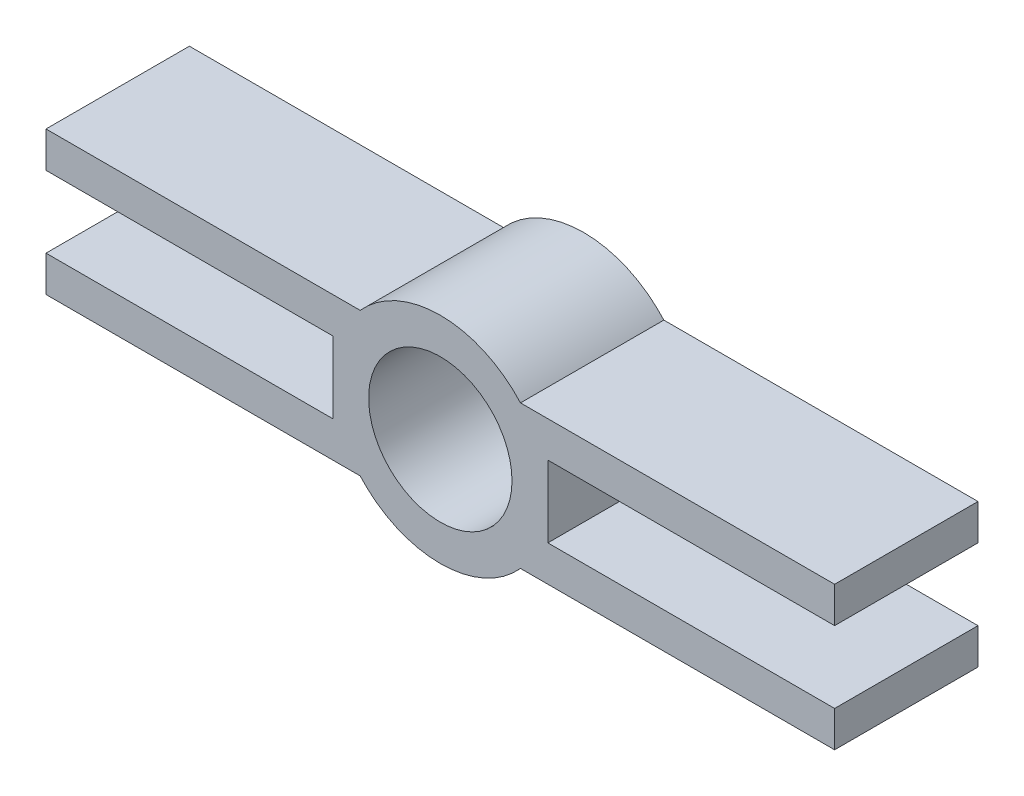
SolidWorks part; units mm, degrees
ref_plane "Front Plane" through (0, 0, 0) normal (0, 0, 1) x (1, 0, 0)
ref_plane "Top Plane" through (0, 0, 0) normal (0, 1, 0) x (1, 0, 0)
ref_plane "Right Plane" through (0, 0, 0) normal (1, 0, 0) x (0, 0, -1)
sketch "Sketch1" plane through (0, 0, 0) normal (0, 0, 1) x (1, 0, 0)
  line L0 (4.851, 0) -> (-50.8, 0)
  line L1 (-50.8, 0) -> (-50.8, 6.35)
  line L2 (-50.8, 6.35) -> (0, 6.35)
  line L3 (0, 6.35) -> (0, 19.05)
  line L4 (0, 19.05) -> (-50.8, 19.05)
  line L5 (-50.8, 19.05) -> (-50.8, 25.4)
  line L6 (-50.8, 25.4) -> (4.851, 25.4)
  line L7 (-50.8, 19.05) -> (-97.7976, 19.05) construction
  line L8 (-97.7976, 19.05) -> (-97.7976, 6.35) construction
  line L9 (-97.7976, 6.35) -> (-50.8, 6.35) construction
  line L10 (0, 12.7) -> (6.35, 12.7) construction
  line L11 (6.35, 12.7) -> (6.35, 4.7841) construction
  line L12 (31.75, 12.7) -> (31.75, 4.7841) construction
  line L13 (19.05, 25.4) -> (19.05, -5.9402) construction
  line L14 (88.9, 0) -> (88.9, 6.35)
  line L15 (88.9, 19.05) -> (88.9, 25.4)
  line L16 (38.1, 12.7) -> (31.75, 12.7) construction
  line L17 (88.9, 25.4) -> (33.249, 25.4)
  line L18 (38.1, 19.05) -> (88.9, 19.05)
  line L19 (38.1, 6.35) -> (38.1, 19.05)
  line L20 (88.9, 6.35) -> (38.1, 6.35)
  line L21 (33.249, 0) -> (88.9, 0)
  circle A0 centre (19.05, 12.7) radius 12.7
  arc A1 (4.851, 0) -> (33.249, 0) centre (19.05, 12.7) ccw
  arc A2 (33.249, 25.4) -> (4.851, 25.4) centre (19.05, 12.7) ccw
  dimension "D1" = 25.4
  dimension "D2" = 6.35
  dimension "D3" = 12.7
  dimension "D4" = 6.35
  dimension "D5" = 50.8
extrude "Boss-Extrude1" add sketch "Sketch1" along normal blind 25.4
